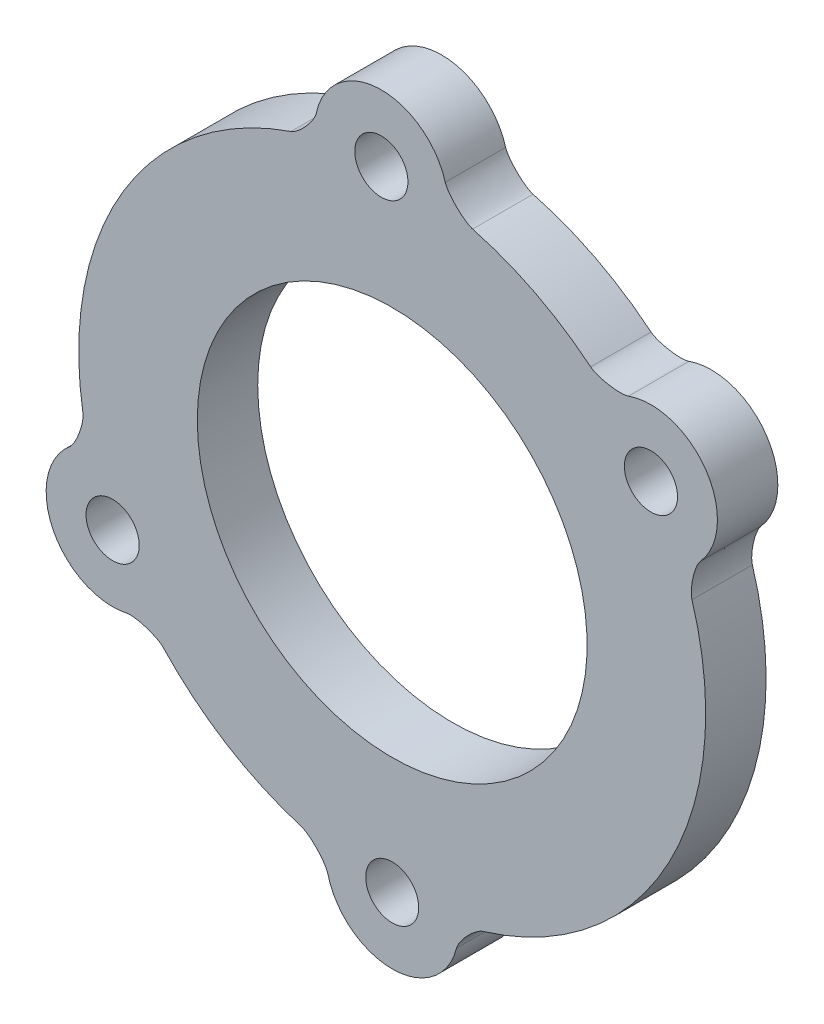
SolidWorks part; units mm, degrees
ref_plane "Front Plane" through (0, 0, 0) normal (0, 0, 1) x (1, 0, 0)
ref_plane "Top Plane" through (0, 0, 0) normal (0, 1, 0) x (1, 0, 0)
ref_plane "Right Plane" through (0, 0, 0) normal (1, 0, 0) x (0, 0, -1)
sketch "Sketch1" plane through (0, 0, 0) normal (0, 0, 1) x (1, 0, 0)
  line L0 (0, -25.0694) -> (0, -36.6594) construction
  line L1 (0, -36.6594) -> (0, -36.6753) construction
  line L2 (-3.4028, -40.1762) -> (-33.2556, -19.7923) construction
  line L3 (0, 0) -> (-22.4957, -11.0643) construction
  line L4 (30.4804, 20.3681) -> (20.8439, 13.9287) construction
  line L5 (-22.4936, -11.0633) -> (-22.4944, -11.067)
  line L6 (-22.4957, -11.0643) -> (-32.8922, -16.187) construction
  line L7 (31.4537, 25.2263) -> (-1.4057, 40.2955) construction
  line L8 (-1.4057, 40.2955) -> (0, 0) construction
  line L9 (-0.874, 25.0542) -> (-1.2783, 36.6442) construction
  line L10 (-1.2783, 36.6442) -> (-1.3976, 40.0621) construction
  arc A0 (3.4028, -40.1762) -> (35.2638, 19.549) centre (0, 0) ccw
  circle A1 centre (0, 0) radius 25.0694
  circle A2 centre (0, -40.0794) radius 3.4042
  circle A3 centre (33.2789, 22.334) radius 3.42
  arc A4 (31.4537, 25.2263) -> (-37.5553, -14.6733) centre (0, 0) ccw
  arc A5 (37.4726, 14.8832) -> (27.9728, 29.0383) centre (33.2789, 22.334) ccw
  arc A6 (-8.5081, -39.4121) -> (8.5081, -39.4121) centre (0, -40.0794) ccw
  circle A7 centre (-35.96, -17.6986) radius 3.4201
  arc A8 (-34.5359, -20.8081) -> (-3.4028, -40.1762) centre (0, 0) ccw
  arc A9 (-39.1222, -9.7547) -> (-31.5942, -25.0501) centre (-35.96, -17.6986) ccw
  circle A10 centre (-1.3976, 40.0621) radius 3.42
  arc A11 (7.144, 39.6821) -> (-9.8919, 39.0878) centre (-1.3976, 40.0621) ccw
  point P10 (30.4804, 20.3681)
  dimension "D1" = 80.64
  dimension "D2" = 11.59
  dimension "D4" = 5.13
  dimension "D7" = 5.13
  dimension "D8" = 5.13
  dimension "D14" = 5.13
  dimension "D3" = 3.42
  dimension "D5" = 11.59
  dimension "D6" = 3.42
  dimension "D9" = 11.59
  dimension "D10" = 3.42
  dimension "D11" = 36.15
  dimension "D12" = 11.59
  dimension "D13" = 3.42
extrude "Boss-Extrude1" add sketch "Sketch1" along normal blind 7.77 contours A10 A4 A7 A8 A2 A0 A3 A1 | A0 A5 A4 A3 | A4 A11 A10 | A4 A9 A8 A7 | A8 A6 A0 A2 region at (3.5177, -40.1294, 0) region at (0, -44.0112, 0) region at (36.5509, 24.5299, 0) region at (-39.4953, -19.4386, 0) region at (-1.5348, 43.9969, 0)
fillet "Fillet1" radius 5 8 edges at (27.9728, 29.0383, 3.885) (37.4726, 14.8832, 3.885) (7.144, 39.6821, 3.885) (-9.8919, 39.0878, 3.885) (-39.1222, -9.7547, 3.885) (-31.5942, -25.0501, 3.885) (-8.5081, -39.4121, 3.885) (8.5081, -39.4121, 3.885) conic radius 10
